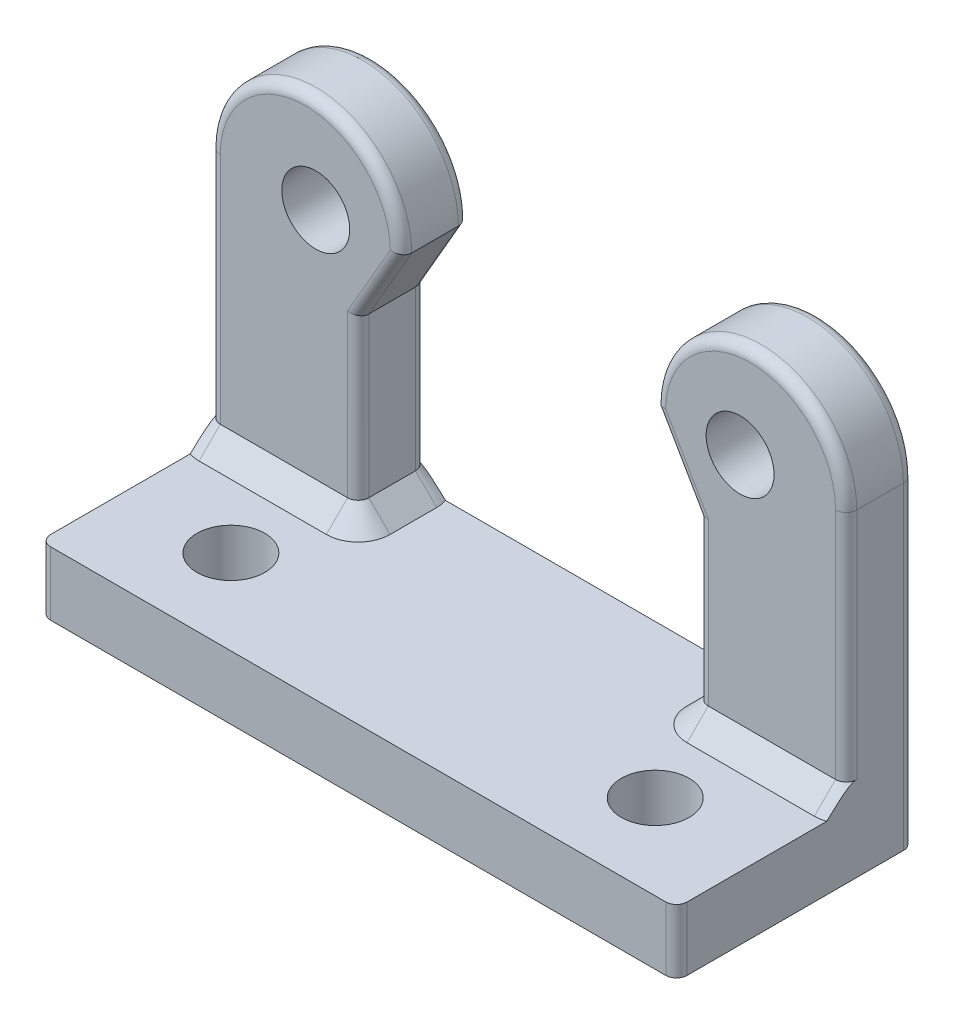
SolidWorks part; units mm, degrees
ref_plane "Front Plane" through (0, 0, 0) normal (0, 0, 1) x (1, 0, 0)
ref_plane "Top Plane" through (0, 0, 0) normal (0, 1, 0) x (1, 0, 0)
ref_plane "Right Plane" through (0, 0, 0) normal (1, 0, 0) x (0, 0, -1)
sketch "Sketch1" plane through (0, 0, 0) normal (0, 0, 1) x (1, 0, 0)
  line L0 (-10, 12) -> (10, 12) construction
  line L1 (-15, -3) -> (15, -3)
  line L2 (-15, -3) -> (-15, 12)
  line L3 (-15, 12) -> (-10, 12) construction
  line L4 (15, -3) -> (15, 12)
  line L5 (0, 12) -> (0, 0) construction
  line L6 (-8, 8.5) -> (8, 8.5) construction
  line L7 (10, 12) -> (15, 12) construction
  line L8 (-8, 8.5) -> (-5.9793, 12)
  line L9 (8, 8.5) -> (5.9793, 12)
  line L23 (-8, 8.5) -> (-8, 0)
  line L30 (-8, 0) -> (8, 0)
  line L31 (8, 0) -> (8, 8.5)
  arc A0 (-15, 12) -> (-5.9793, 12) centre (-10.4896, 12) cw
  arc A1 (15, 12) -> (5.9793, 12) centre (10.4896, 12) ccw
  circle A2 centre (-10, 12) radius 1.6
  circle A3 centre (10, 12) radius 1.6
  point P0 (0, 0)
  point P14 (-10, 12)
  point P15 (10, 12)
  point P26 (0, 0)
  dimension "D1" = 3.2
  dimension "D2" = 3
  dimension "D3" = 30
  dimension "D4" = 16
  dimension "D5" = 60
  dimension "D6" = 20
  dimension "D7" = 60
  dimension "D8" = 12
  dimension "D9" = 3.5
extrude "Boss-Extrude1" add sketch "Sketch1" along normal blind 3.2
sketch "Sketch2" plane through (0, 0, 3.2) normal (0, 0, 1) x (1, 0, 0)
  line L0 (15, -3) -> (15, 12) construction
  line L1 (-15, -3) -> (15, -3)
  line L2 (-15, -3) -> (-15, 0)
  line L3 (-15, 0) -> (15, 0)
  line L4 (15, -3) -> (15, 0)
extrude "Boss-Extrude2" add sketch "Sketch2" along normal blind 8
sketch "Sketch3" plane through (0, 0, 0) normal (0, 1, 0) x (1, 0, 0)
  line L0 (-15, -7.2) -> (15, -7.2) construction
  line L2 (-15, -11.2) -> (-15, -3.2) construction
  line L3 (15, -11.2) -> (15, -3.2) construction
  line L4 (-10, -7.2) -> (10, -7.2) construction
  circle A0 centre (-10, -7.2) radius 1.6
  circle A1 centre (10, -7.2) radius 1.6
  point P14 (0, -7.2)
  dimension "D2" = 3.2
  dimension "D1" = 20
extrude "Cut-Extrude1" cut sketch "Sketch3" against normal through all
fillet "Fillet1" radius 0.5 18 edges at (8, 4.25, 3.2) (-15, 6, 3.2) (-8, 4.25, 0) (8, 4.25, 0) (15, 6, 3.2) (-8, 4.25, 3.2) (-15, 4.5, 0) (15, 4.5, 0) (-15, -1.5, 11.2) (15, -1.5, 11.2) (10.4896, 16.5104, 3.2) (-10.4896, 16.5104, 0) (10.4896, 16.5104, 0) (-10.4896, 16.5104, 3.2) (-6.9896, 10.25, 0) (-6.9896, 10.25, 3.2) (6.9896, 10.25, 0) (6.9896, 10.25, 3.2)
chamfer "Chamfer1" distance 1 angle 45 10 edges at (8.1464, 0, 0.1464) (8, 0, 1.6) (14.8536, 0, 3.0536) (8.1464, 0, 3.0536) (11.5, 0, 3.2) (-8.1464, 0, 0.1464) (-8, 0, 1.6) (-8.1464, 0, 3.0536) (-14.8536, 0, 3.0536) (-11.5, 0, 3.2)
